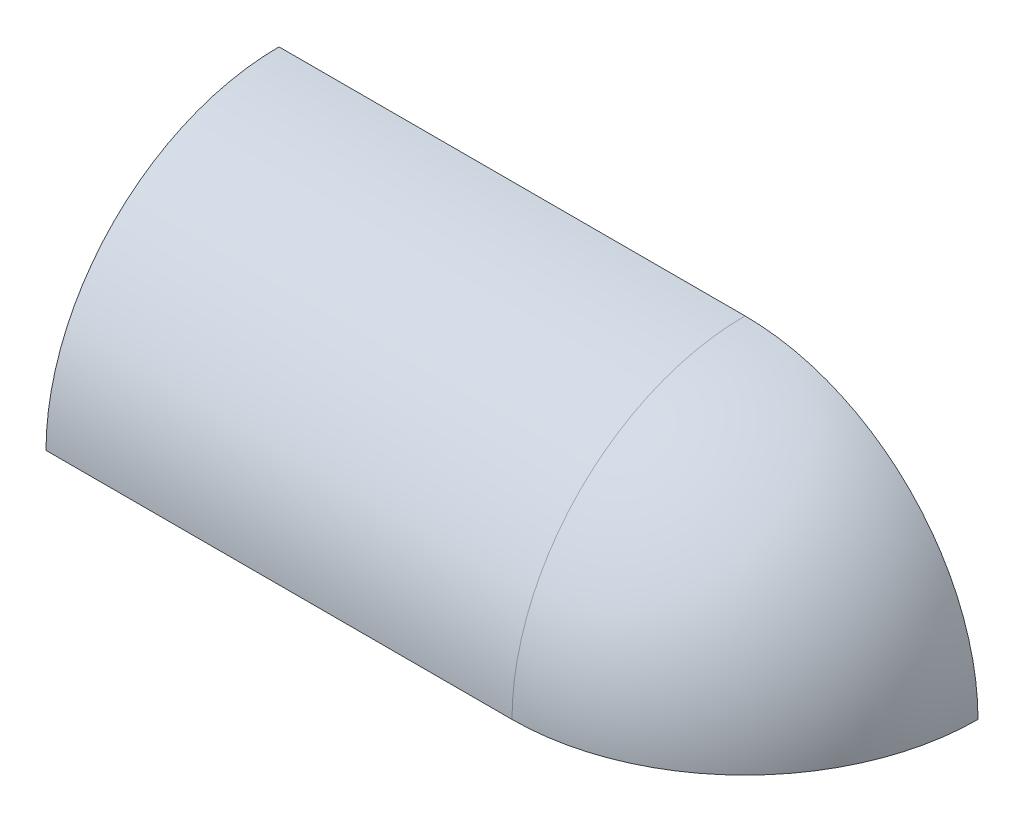
SolidWorks part; units mm, degrees
note: '?' marks a value the reader was unsure of.
ref_plane "Front Plane" through (0, 0, 0) normal (0, 0, 1) x (1, 0, 0)
ref_plane "Top Plane" through (0, 0, 0) normal (0, 1, 0) x (1, 0, 0)
ref_plane "Right Plane" through (0, 0, 0) normal (1, 0, 0) x (0, 0, -1)
sketch "Sketch2" plane through (0, 0, 0) normal (1, 0, 0) x (0, 0, -1)
  circle A0 centre (0, 0) radius 50.8
  dimension "D1" = 101.6
extrude "Boss-Extrude1" add sketch "Sketch2" along normal mid plane 203.2
sketch "Sketch3" plane through (0, 0, 0) normal (1, 0, 0) x (0, 0, -1)
  circle A0 centre (0, 0) radius 47.625
  dimension "D1" = 95.25
extrude "Cut-Extrude1" cut sketch "Sketch3" along normal mid plane 203.2
sketch "Sketch4" plane through (0, 0, 0) normal (0, 0, 1) x (1, 0, 0)
  line L0 (-152.4, 0) -> (-101.6, 0) construction
  line L2 (-101.6, 50.8) -> (-101.6, 0) construction
  arc A0 (-101.6, 50.8) -> (-152.4, 0) centre (-101.6, 0) ccw
  dimension "D1" = 50.8
revolve "Revolve-Thin1" add sketch "Sketch4" angle 360 about L0 wall 3.175
sketch "Sketch5" plane through (0, 0, 0) normal (0, 0, 1) x (1, 0, 0)
  line L0 (101.6, -50.8) -> (101.6, 50.8) construction
  line L1 (152.4, 0) -> (101.6, 0) construction
  line L2 (101.6, 0) -> (101.6, 50.8) construction
  arc A0 (101.6, 50.8) -> (152.4, 0) centre (101.6, 0) cw
revolve "Revolve-Thin2" add sketch "Sketch5" angle 360 about L1
sketch "Sketch9" plane through (0, 0, 0) normal (0, 0, 1) x (1, 0, 0)
  line L2 (-485.2228, -983.8137) -> (2435.7772, -983.8137)
  line L3 (-485.2228, -983.8137) -> (-485.2228, 921.1863)
  line L4 (-485.2228, 921.1863) -> (2435.7772, 921.1863)
  line L5 (2435.7772, -983.8137) -> (2435.7772, 921.1863)
  dimension "D1" = 1905
  dimension "D2" = 2921
extrude "Cut-Extrude4" cut sketch "Sketch9" against normal blind 1828.8
sketch "Sketch10" plane through (0, 0, 0) normal (0, 1, 0) x (1, 0, 0)
  line L1 (-554.2297, 500.0268) -> (2360.1686, 500.0268)
  line L2 (-554.2297, 500.0268) -> (-554.2297, -769.9039)
  line L3 (-554.2297, -769.9039) -> (2360.1686, -769.9039)
  line L4 (2360.1686, 500.0268) -> (2360.1686, -769.9039)
extrude "Cut-Extrude7" cut sketch "Sketch10" against normal blind 508
sketch "Sketch11" plane through (0, 0, 0) normal (1, 0, 0) x (0, 0, -1)
  line L1 (97.1467, -83.0662) -> (-184.7648, -83.0662)
  line L2 (97.1467, -83.0662) -> (97.1467, 150.2102)
  line L3 (97.1467, 150.2102) -> (-184.7648, 150.2102)
  line L4 (-184.7648, -83.0662) -> (-184.7648, 150.2102)
extrude "Cut-Extrude8" cut sketch "Sketch11" against normal through all
ref_axis "Axis1" through (101.6, 0, 0) along (-1, 0, 0)?
